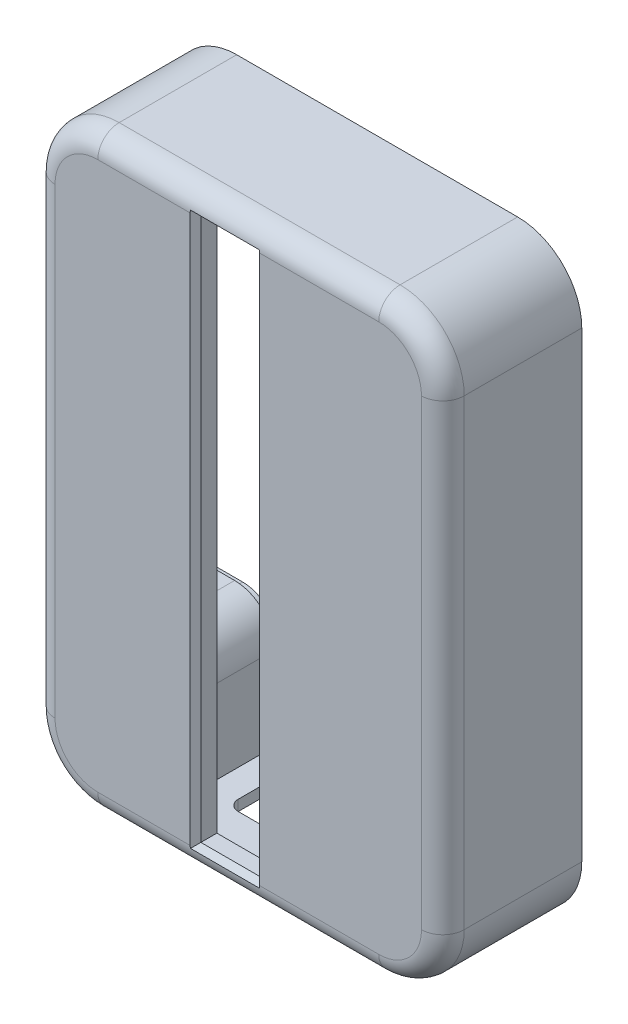
SolidWorks part; units mm, degrees
ref_plane "Front Plane" through (0, 0, 0) normal (0, 0, 1) x (1, 0, 0)
ref_plane "Top Plane" through (0, 0, 0) normal (0, 1, 0) x (1, 0, 0)
ref_plane "Right Plane" through (0, 0, 0) normal (1, 0, 0) x (0, 0, -1)
sketch "Sketch1" plane through (0, 0, 0) normal (0, 0, 1) x (1, 0, 0)
  line L0 (-1, 27.54) -> (-1, 1) construction
  line L2 (35.29, 1) -> (35.29, 44.26) construction
  line L4 (-1, 44.26) -> (-1, 35.94) construction
  line L5 (-1, 27.44) -> (-1, 1)
  line L7 (35.29, 1) -> (35.29, 44.26)
  line L8 (30.29, 49.26) -> (4, 49.26)
  line L9 (-1, 44.26) -> (-1, 36.04)
  line L10 (-2, 27.54) -> (-2, 1) construction
  line L12 (36.29, 1) -> (36.29, 44.26) construction
  line L14 (-2, 44.26) -> (-2, 35.94) construction
  line L15 (-2, 27.44) -> (-2, 1)
  line L17 (36.29, 1) -> (36.29, 44.26)
  line L18 (30.29, 50.26) -> (4, 50.26)
  line L19 (-2, 44.26) -> (-2, 36.04)
  line L22 (-2, 27.44) -> (-1, 27.44)
  line L23 (-2, 36.04) -> (-1, 36.04)
  line L24 (-1, 35.94) -> (-2, 35.94) construction
  line L25 (-2, 27.54) -> (-1, 27.54) construction
  line L26 (35.29, 22.63) -> (7.5344, 22.63) construction
  line L32 (30.29, -5) -> (4, -5)
  line L33 (30.29, -4) -> (4, -4)
  arc A1 (35.29, 1) -> (30.29, -4) centre (30.29, 1) cw
  arc A2 (35.29, 44.26) -> (30.29, 49.26) centre (30.29, 44.26) ccw construction
  arc A3 (4, 49.26) -> (-1, 44.26) centre (4, 44.26) ccw construction
  arc A6 (35.29, 44.26) -> (30.29, 49.26) centre (30.29, 44.26) ccw
  arc A7 (4, 49.26) -> (-1, 44.26) centre (4, 44.26) ccw
  arc A8 (36.29, 1) -> (30.29, -5) centre (30.29, 1) cw
  arc A10 (36.29, 44.26) -> (30.29, 50.26) centre (30.29, 44.26) ccw construction
  arc A11 (4, 50.26) -> (-2, 44.26) centre (4, 44.26) ccw construction
  arc A14 (36.29, 44.26) -> (30.29, 50.26) centre (30.29, 44.26) ccw
  arc A15 (4, 50.26) -> (-2, 44.26) centre (4, 44.26) ccw
  arc A16 (4, -4) -> (-1, 1) centre (4, 1) cw
  arc A17 (4, -5) -> (-2, 1) centre (4, 1) cw
  dimension "D1" = 0.1
  dimension "D2" = 0.1
extrude "Boss-Extrude1" add sketch "Sketch1" along normal blind 10 contours L15 A17 L5 L22 | L7 A6 L8 A7 L9 L23 L19 A15 L18 A14 L17 A8 L32 A17 L15 L22 L5 A16 L33 A1 region at (-1.6723, 14.22, 0)
sketch "Sketch12" plane through (0, 0, 10) normal (0, 0, 1) x (1, 0, 0)
  line L0 (-2, 36.04) -> (-1, 36.04)
  line L1 (-1, 36.04) -> (-1, 27.44)
  line L2 (-1, 27.44) -> (-2, 27.44)
  line L3 (-2, 27.44) -> (-2, 36.04)
extrude "Boss-Extrude8" add sketch "Sketch12" against normal blind 5
sketch "Sketch8" plane through (0, 0, 10) normal (0, 0, 1) x (1, 0, 0)
  line L10 (-2, 44.26) -> (-2, 1) construction
  line L11 (30.29, -5) -> (4, -5) construction
  line L12 (36.29, 1) -> (36.29, 44.26) construction
  line L13 (30.29, 50.26) -> (4, 50.26) construction
  line L14 (-2, 44.26) -> (-2, 1)
  line L15 (30.29, -5) -> (4, -5)
  line L16 (36.29, 1) -> (36.29, 44.26)
  line L17 (30.29, 50.26) -> (4, 50.26)
  arc A8 (-2, 1) -> (4, -5) centre (4, 1) ccw construction
  arc A9 (30.29, -5) -> (36.29, 1) centre (30.29, 1) ccw construction
  arc A10 (36.29, 44.26) -> (30.29, 50.26) centre (30.29, 44.26) ccw construction
  arc A11 (4, 50.26) -> (-2, 44.26) centre (4, 44.26) ccw construction
  arc A12 (-2, 1) -> (4, -5) centre (4, 1) ccw
  arc A13 (30.29, -5) -> (36.29, 1) centre (30.29, 1) ccw
  arc A14 (36.29, 44.26) -> (30.29, 50.26) centre (30.29, 44.26) ccw
  arc A15 (4, 50.26) -> (-2, 44.26) centre (4, 44.26) ccw
extrude "Boss-Extrude5" add sketch "Sketch8" along normal blind 3 contours A14 L17 A15 L14 A12 L15 A13 L16
sketch "Sketch10" plane through (0, 0, 10) normal (0, 0, -1) x (-1, 0, 0)
  line L4 (-30.29, 50.26) -> (-4, 50.26) construction
  line L6 (-17.145, 50.26) -> (-17.145, 41.4835) construction
  line L7 (-35.29, 22.63) -> (-17.145, 22.63) construction
  line L14 (-35.29, 1) -> (-35.29, 44.26) construction
  line L15 (-17.145, -5) -> (-17.145, 3.7765) construction
  line L16 (1, 44.26) -> (1, 36.04) construction
  line L17 (-30.29, 49.26) -> (-26.73, 49.26)
  line L18 (1, 44.26) -> (1, 40.7)
  line L19 (-3.81, 40.7) -> (1, 40.7)
  line L20 (-7.56, 44.45) -> (-7.56, 49.26)
  line L21 (1, 40.7) -> (1, 44.26)
  line L22 (1, 27.44) -> (1, 1) construction
  line L24 (1, 7.56) -> (1, 1)
  line L26 (-7.56, 3.81) -> (-7.56, -4)
  line L27 (-3.81, 7.56) -> (1, 7.56)
  line L28 (-7.56, -4) -> (-4, -4)
  line L29 (-4, 49.26) -> (-7.56, 49.26)
  line L30 (-26.73, -4) -> (-30.29, -4)
  line L31 (-30.48, 7.56) -> (-35.29, 7.56)
  line L32 (-26.73, 3.81) -> (-26.73, -4)
  line L33 (-35.29, 7.56) -> (-35.29, 1)
  line L34 (-35.29, 40.7) -> (-35.29, 44.26)
  line L35 (-26.73, 44.45) -> (-26.73, 49.26)
  line L36 (-30.48, 40.7) -> (-35.29, 40.7)
  line L37 (-35.29, 44.26) -> (-35.29, 40.7)
  circle A5 centre (-3.81, 44.45) radius 1.75
  arc A8 (1, 44.26) -> (-4, 49.26) centre (-4, 44.26) ccw construction
  arc A12 (1, 44.26) -> (-4, 49.26) centre (-4, 44.26) ccw
  arc A13 (-7.56, 44.45) -> (-3.81, 40.7) centre (-3.81, 44.45) ccw
  circle A14 centre (-3.81, 3.81) radius 1.75
  circle A15 centre (-3.81, 44.45) radius 3.75 construction
  arc A16 (-3.81, 7.56) -> (-7.56, 3.81) centre (-3.81, 3.81) ccw
  arc A17 (-4, -4) -> (1, 1) centre (-4, 1) ccw construction
  arc A18 (-4, -4) -> (1, 1) centre (-4, 1) ccw
  arc A19 (-30.29, -4) -> (-35.29, 1) centre (-30.29, 1) cw
  circle A20 centre (-3.81, 3.81) radius 3.75 construction
  arc A21 (-30.48, 7.56) -> (-26.73, 3.81) centre (-30.48, 3.81) cw
  circle A22 centre (-30.48, 3.81) radius 1.75
  arc A23 (-26.73, 44.45) -> (-30.48, 40.7) centre (-30.48, 44.45) cw
  arc A24 (-35.29, 44.26) -> (-30.29, 49.26) centre (-30.29, 44.26) cw
  circle A25 centre (-30.48, 44.45) radius 1.75
  point P21 (-0.0551, 44.45)
  point P39 (-0.06, 3.81)
  line M27 (1, 1) -> (1, 44.26)
  arc M28 (1, 44.26) -> (-4, 49.26) centre (-4, 44.26) ccw
  line M29 (-4, 49.26) -> (-30.29, 49.26)
  arc M30 (-30.29, 49.26) -> (-35.29, 44.26) centre (-30.29, 44.26) ccw
  line M31 (-35.29, 44.26) -> (-35.29, 1)
  arc M79 (-4, -4) -> (1, 1) centre (-4, 1) ccw
  arc M80 (-35.29, 1) -> (-30.29, -4) centre (-30.29, 1) ccw
  line M82 (-30.29, -4) -> (-4, -4)
  dimension "D2" = 3.5
  dimension "D3" = 3.5
  dimension "D1" = 2
  dimension "D4" = 2
extrude "Boss-Extrude6" add sketch "Sketch10" along normal blind 10.75 from surface contours M29 M30 M31 | M27 M28 M29 | A21 L31 L32 A22 M31 M80 M82 | L27 A16 L26 A14 M82 M79 M27 region at (28.51, 49.1389, 10) region at (5.78, 49.1389, 10) region at (30.9917, 1.6635, 10) region at (3.2983, 1.6635, 10) starting at face at (17.145, 22.63, 10)
sketch "Sketch11" plane through (0, 0, 10) normal (0, 0, -1) x (-1, 0, 0)
  line L0 (-24.195, -4) -> (-24.195, -5)
  line L1 (-24.195, -5) -> (-10.095, -5)
  line L2 (-10.095, -5) -> (-10.095, -4)
  line L3 (-10.095, -4) -> (-24.195, -4)
  line L4 (-17.145, -5) -> (-17.145, -4) construction
  line L5 (-30.29, -5) -> (-4, -5) construction
  line L6 (-26.73, -4) -> (-7.56, -4) construction
  line L7 (-26.73, -4) -> (-7.56, -4) construction
  point P19 (-17.145, -5)
  dimension "D1" = 14.1
extrude "Boss-Extrude7" add sketch "Sketch11" along normal blind 1.5
fillet "Fillet1" radius 2 8 edges at (17.145, 50.26, 13) (34.5326, 48.5026, 13) (-0.2426, 48.5026, 13) (36.29, 22.63, 13) (34.5326, -3.2426, 13) (17.145, -5, 13) (-0.2426, -3.2426, 13) (-2, 22.63, 13)
sketch "Sketch13" plane through (0, -5, 0) normal (0, -1, 0) x (1, 0, 0)
  line L0 (17.145, 0) -> (17.145, 13) construction
  line L1 (30.29, 0) -> (4, 0) construction
  line L2 (4, 13) -> (30.29, 13) construction
  line L4 (24.145, 0) -> (10.145, 0)
  line L5 (24.145, 0) -> (24.145, 7)
  line L6 (24.145, 7) -> (10.145, 7)
  line L7 (10.145, 0) -> (10.145, 7)
  line L8 (24.145, 0) -> (10.145, 7) construction
  line L9 (24.145, 7) -> (10.145, 0) construction
  point P6 (17.145, 3.5)
  dimension "D1" = 6
  dimension "D2" = 14
extrude "Cut-Extrude2" cut sketch "Sketch13" against normal up to next
fillet "Fillet2" radius 1 4 edges at (24.145, -4.5, 7) (10.145, -4.5, 7) (-1.5, 27.44, 5) (-1.5, 36.04, 5)
sketch "Sketch14" plane through (0, 0, 10) normal (0, 0, -1) x (-1, 0, 0)
  line L0 (-17.145, 49.26) -> (-17.145, -4) construction
  line L1 (-26.73, 49.26) -> (-7.56, 49.26) construction
  line L2 (-11.145, -4) -> (-23.145, -4) construction
  line L4 (-11.645, -4) -> (-22.645, -4)
  line L5 (-11.645, -4) -> (-11.645, 49.26)
  line L6 (-11.645, 49.26) -> (-22.645, 49.26)
  line L7 (-22.645, -4) -> (-22.645, 49.26)
  line L8 (-11.645, -4) -> (-22.645, 49.26) construction
  line L9 (-11.645, 49.26) -> (-22.645, -4) construction
  point P6 (-17.145, 22.63)
  dimension "D1" = 11
extrude "Cut-Extrude3" cut sketch "Sketch14" against normal blind 1
sketch "Sketch15" plane through (0, 0, 11) normal (0, 0, -1) x (-1, 0, 0)
  line L0 (-22.645, 49.26) -> (-22.645, -4) construction
  line L1 (-13.145, 48.01) -> (-18.645, 48.01)
  line L2 (-13.145, 48.01) -> (-13.145, -2.75)
  line L3 (-13.145, -2.75) -> (-18.645, -2.75)
  line L4 (-18.645, 48.01) -> (-18.645, -2.75)
  line L5 (-11.145, -4) -> (-23.145, -4) construction
  line L6 (-26.73, 49.26) -> (-7.56, 49.26) construction
  dimension "D1" = 5.5
  dimension "D2" = 4
  dimension "D3" = 1.25
  dimension "D4" = 1.25
extrude "Cut-Extrude4" cut sketch "Sketch15" against normal through all
sketch "Sketch17" plane through (0, 0, 11) normal (0, 0, -1) x (-1, 0, 0)
  line L0 (-26.73, 49.26) -> (-7.56, 49.26) construction
  line L1 (-22.645, 49.26) -> (-22.645, -4) construction
  line L2 (-22.645, 12.86) -> (-18.645, 12.86)
  line L3 (-18.645, 48.01) -> (-18.645, -2.75) construction
  line L4 (-18.645, 12.86) -> (-18.645, 7.86)
  line L5 (-18.645, 7.86) -> (-22.645, 7.86)
  line L6 (-22.645, 7.86) -> (-22.645, 12.86)
  line L7 (-22.645, 33.26) -> (-18.645, 33.26)
  line L8 (-18.645, 33.26) -> (-18.645, 38.26)
  line L9 (-18.645, 38.26) -> (-22.645, 38.26)
  line L10 (-22.645, 38.26) -> (-22.645, 33.26)
  circle A0 centre (-20.145, 35.76) radius 1
  circle A1 centre (-20.145, 10.36) radius 1
  line M4 (-18.645, -2.75) -> (-18.645, 48.01)
  line M6 (-22.645, 49.26) -> (-22.645, -4)
  dimension "D1" = 2
  dimension "D2" = 13.5
  dimension "D3" = 2.5
  dimension "D4" = 25.4
  dimension "D5" = 2.5
  dimension "D6" = 2.5
  dimension "D7" = 2.5
  dimension "D8" = 2.5
extrude "Boss-Extrude9" add sketch "Sketch17" along normal blind 1 contours L5 L2 A1 M4 M6 | L9 L7 A0 M4 M6 region at (20.645, 12.796, 11) region at (22.581, 35.76, 11)
chamfer "Chamfer1" distance 0.5 angle 45 4 edges at (15.895, 48.01, 13) (18.645, 22.63, 13) (15.895, -2.75, 13) (13.145, 22.63, 13)
sketch "Sketch18" plane through (0, 0, 11) normal (0, 0, -1) x (-1, 0, 0)
  circle A0 centre (-20.145, 10.36) radius 1 construction
  circle A1 centre (-20.145, 35.76) radius 1 construction
  circle A2 centre (-20.145, 10.36) radius 1
  circle A3 centre (-20.145, 35.76) radius 1
extrude "Cut-Extrude5" cut sketch "Sketch18" against normal blind 1
sketch "Sketch19" plane through (0, 0, -0.75) normal (0, 0, -1) x (-1, 0, 0)
  line L0 (-25.23, 50.76) -> (-30.29, 50.76)
  line L1 (-36.79, 44.26) -> (-36.79, 39.2)
  line L2 (-36.79, 39.2) -> (-30.48, 39.2)
  line L3 (-25.23, 44.45) -> (-25.23, 50.76)
  line L8 (-27.23, 48.76) -> (-30.29, 48.76)
  line L9 (-34.79, 44.26) -> (-34.79, 41.2)
  line L10 (-27.23, 44.45) -> (-27.23, 48.76)
  line L11 (-34.79, 41.2) -> (-30.48, 41.2)
  line L12 (-27.23, 48.76) -> (-30.29, 48.76)
  line L13 (-34.79, 44.26) -> (-34.79, 41.2)
  line L14 (-27.23, 44.45) -> (-27.23, 48.76)
  line L15 (-34.79, 41.2) -> (-30.48, 41.2)
  line L52 (-4, 50.76) -> (-9.06, 50.76)
  line L53 (-9.06, 50.76) -> (-9.06, 44.45)
  line L54 (-3.81, 39.2) -> (2.5, 39.2)
  line L55 (2.5, 39.2) -> (2.5, 44.26)
  line L56 (-4, 48.76) -> (-7.06, 48.76)
  line L57 (-7.06, 48.76) -> (-7.06, 44.45)
  line L58 (-3.81, 41.2) -> (0.5, 41.2)
  line L59 (0.5, 41.2) -> (0.5, 44.26)
  line L60 (-4, 48.76) -> (-7.06, 48.76)
  line L61 (-7.06, 48.76) -> (-7.06, 44.45)
  line L62 (-3.81, 41.2) -> (0.5, 41.2)
  line L63 (0.5, 41.2) -> (0.5, 44.26)
  line L68 (-30.29, -5.5) -> (-25.23, -5.5)
  line L69 (-25.23, -5.5) -> (-25.23, 3.81)
  line L70 (-30.48, 9.06) -> (-36.79, 9.06)
  line L71 (-36.79, 9.06) -> (-36.79, 1)
  line L72 (-30.29, -3.5) -> (-27.23, -3.5)
  line L73 (-27.23, -3.5) -> (-27.23, 3.81)
  line L74 (-30.48, 7.06) -> (-34.79, 7.06)
  line L75 (-34.79, 7.06) -> (-34.79, 1)
  line L76 (-30.29, -3.5) -> (-27.23, -3.5)
  line L77 (-27.23, -3.5) -> (-27.23, 3.81)
  line L78 (-30.48, 7.06) -> (-34.79, 7.06)
  line L79 (-34.79, 7.06) -> (-34.79, 1)
  line L84 (-9.06, -5.5) -> (-4, -5.5)
  line L85 (2.5, 1) -> (2.5, 9.06)
  line L86 (2.5, 9.06) -> (-3.81, 9.06)
  line L87 (-9.06, 3.81) -> (-9.06, -5.5)
  line L88 (-7.06, -3.5) -> (-4, -3.5)
  line L89 (0.5, 1) -> (0.5, 7.06)
  line L90 (0.5, 7.06) -> (-3.81, 7.06)
  line L91 (-7.06, 3.81) -> (-7.06, -3.5)
  line L92 (-7.06, -3.5) -> (-4, -3.5)
  line L93 (0.5, 1) -> (0.5, 7.06)
  line L94 (0.5, 7.06) -> (-3.81, 7.06)
  line L95 (-7.06, 3.81) -> (-7.06, -3.5)
  arc A0 (-30.29, 50.76) -> (-36.79, 44.26) centre (-30.29, 44.26) ccw
  arc A1 (-30.48, 39.2) -> (-25.23, 44.45) centre (-30.48, 44.45) ccw
  arc A4 (-30.29, 48.76) -> (-34.79, 44.26) centre (-30.29, 44.26) ccw
  arc A5 (-30.48, 41.2) -> (-27.23, 44.45) centre (-30.48, 44.45) ccw
  arc A6 (-30.29, 48.76) -> (-34.79, 44.26) centre (-30.29, 44.26) ccw
  arc A7 (-30.48, 41.2) -> (-27.23, 44.45) centre (-30.48, 44.45) ccw
  arc A20 (-9.06, 44.45) -> (-3.81, 39.2) centre (-3.81, 44.45) ccw
  arc A21 (2.5, 44.26) -> (-4, 50.76) centre (-4, 44.26) ccw
  arc A22 (-7.06, 44.45) -> (-3.81, 41.2) centre (-3.81, 44.45) ccw
  arc A23 (0.5, 44.26) -> (-4, 48.76) centre (-4, 44.26) ccw
  arc A24 (-7.06, 44.45) -> (-3.81, 41.2) centre (-3.81, 44.45) ccw
  arc A25 (0.5, 44.26) -> (-4, 48.76) centre (-4, 44.26) ccw
  arc A28 (-25.23, 3.81) -> (-30.48, 9.06) centre (-30.48, 3.81) ccw
  arc A29 (-36.79, 1) -> (-30.29, -5.5) centre (-30.29, 1) ccw
  arc A30 (-27.23, 3.81) -> (-30.48, 7.06) centre (-30.48, 3.81) ccw
  arc A31 (-34.79, 1) -> (-30.29, -3.5) centre (-30.29, 1) ccw
  arc A32 (-27.23, 3.81) -> (-30.48, 7.06) centre (-30.48, 3.81) ccw
  arc A33 (-34.79, 1) -> (-30.29, -3.5) centre (-30.29, 1) ccw
  arc A36 (-4, -5.5) -> (2.5, 1) centre (-4, 1) ccw
  arc A37 (-3.81, 9.06) -> (-9.06, 3.81) centre (-3.81, 3.81) ccw
  arc A38 (-4, -3.5) -> (0.5, 1) centre (-4, 1) ccw
  arc A39 (-3.81, 7.06) -> (-7.06, 3.81) centre (-3.81, 3.81) ccw
  arc A40 (-4, -3.5) -> (0.5, 1) centre (-4, 1) ccw
  arc A41 (-3.81, 7.06) -> (-7.06, 3.81) centre (-3.81, 3.81) ccw
  dimension "D1" = 0.5
  dimension "D2" = 2
  dimension "D3" = 0.5
  dimension "D4" = 2
  dimension "D5" = 0.5
  dimension "D6" = 2
  dimension "D7" = 0.5
  dimension "D8" = 2
extrude "Cut-Extrude7" cut sketch "Sketch19" against normal up to surface (0.75 mm away) up to face at (20.3404, 28.0872, 0)
